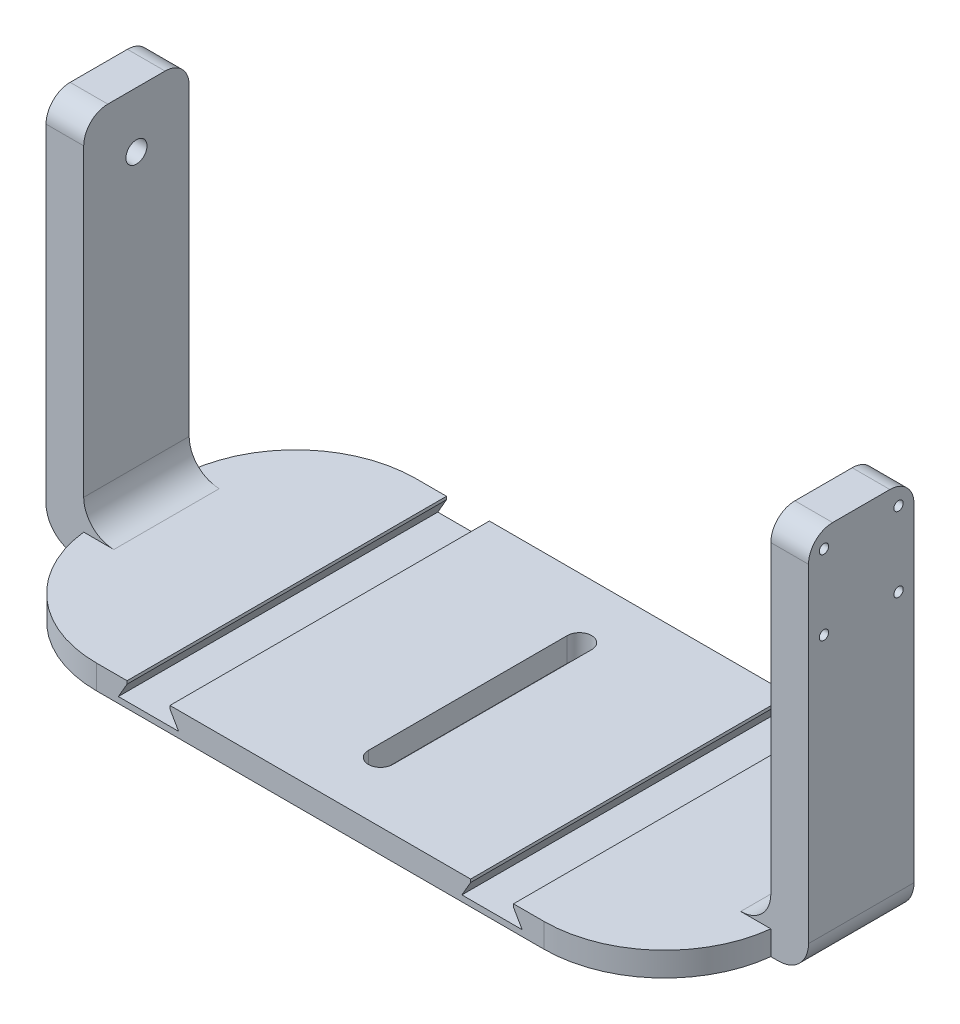
SolidWorks part; units mm, degrees
ref_plane "Front Plane" through (0, 0, 0) normal (0, 0, 1) x (1, 0, 0)
ref_plane "Top Plane" through (0, 0, 0) normal (0, 1, 0) x (1, 0, 0)
ref_plane "Right Plane" through (0, 0, 0) normal (1, 0, 0) x (0, 0, -1)
sketch "Sketch1" plane through (0, 0, 0) normal (0, 0, 1) x (1, 0, 0)
  line L0 (114, 8) -> (114, 0) construction
  line L1 (0, 0) -> (228, 0)
  line L2 (0, 0) -> (0, 8)
  line L3 (0, 8) -> (228, 8)
  line L4 (228, 0) -> (228, 8)
  line L5 (49.8868, 8) -> (49.8868, 7)
  line L7 (178.1132, 8) -> (163.8868, 8)
  line L8 (163.8868, 8) -> (163.8868, 7)
  line L9 (163.8868, 7) -> (161, 2)
  line L10 (161, 2) -> (181, 2)
  line L11 (178.1132, 8) -> (178.1132, 7)
  line L12 (178.1132, 7) -> (181, 2)
  line L13 (114, 4) -> (228, 4) construction
  line L14 (49.8868, 8) -> (64.1132, 8)
  line L15 (171, 2) -> (171, 8) construction
  line L16 (64.1132, 8) -> (64.1132, 7)
  line L17 (64.1132, 7) -> (67, 2)
  line L18 (67, 2) -> (47, 2)
  line L19 (49.8868, 7) -> (47, 2)
  line L25 (228, 0) -> (240.5, 0)
  line L26 (228, 0) -> (228, 127)
  line L27 (228, 127) -> (240.5, 127)
  line L28 (240.5, 0) -> (240.5, 127)
  line L29 (0, 0) -> (-12.5, 0)
  line L30 (0, 0) -> (0, 127)
  line L31 (0, 127) -> (-12.5, 127)
  line L32 (-12.5, 0) -> (-12.5, 127)
  point P7 (171, 4)
  dimension "D1" = 228
  dimension "D2" = 8
  dimension "D3" = 1
  dimension "D4" = 1
  dimension "D5" = 60
  dimension "D6" = 60
  dimension "D7" = 20
  dimension "D8" = 2
  dimension "D9" = 12.5
  dimension "D10" = 127
  dimension "D11" = 12.5
  dimension "D12" = 127
extrude "Boss-Extrude1" add sketch "Sketch1" against normal blind 106 contours L19 L5 L3 L2 L1 L4 L11 L12 L10 L9 L8 L16 L17 L18 | L26 L25 L28 L27 | L30 L29 L32 L31 region at (114, 3.9008, 0)
sketch "Sketch2" plane through (0, 127, 0) normal (0, 1, 0) x (1, 0, 0)
  line L0 (0, 106) -> (0, 0) construction
  line L1 (-12.5, 106) -> (0, 106)
  line L2 (-12.5, 106) -> (-12.5, 70.5)
  line L3 (-12.5, 70.5) -> (0, 70.5)
  line L4 (0, 106) -> (0, 70.5)
  line L5 (228, 106) -> (228, 0) construction
  line L6 (-12.5, 0) -> (0, 0)
  line L7 (-12.5, 0) -> (-12.5, 35.5)
  line L8 (-12.5, 35.5) -> (0, 35.5)
  line L9 (0, 0) -> (0, 35.5)
  line L10 (240.5, 106) -> (228, 106)
  line L11 (240.5, 106) -> (240.5, 70.5)
  line L12 (240.5, 70.5) -> (228, 70.5)
  line L13 (228, 106) -> (228, 70.5)
  line L14 (0, 106) -> (228, 106) construction
  line L15 (240.5, 0) -> (228, 0)
  line L16 (240.5, 0) -> (240.5, 35.5)
  line L17 (240.5, 35.5) -> (228, 35.5)
  line L18 (228, 0) -> (228, 35.5)
  line L19 (114, 106) -> (114, 0) construction
  line L20 (64.1132, 0) -> (163.8868, 0) construction
  line L21 (114, 20) -> (114, 86) construction
  line L22 (109.95, 20) -> (109.95, 86)
  line L23 (118.05, 20) -> (118.05, 86)
  line L24 (0, 53) -> (228, 53) construction
  line L27 (0, 106) -> (0, 0) construction
  line L28 (228, 106) -> (228, 0) construction
  arc A0 (109.95, 20) -> (118.05, 20) centre (114, 20) ccw
  arc A1 (118.05, 86) -> (109.95, 86) centre (114, 86) ccw
  point P30 (114, 53)
  point P35 (114, 90.05)
  point P36 (114, 15.95)
  point P41 (114, 106)
  point P44 (114, 53)
  dimension "D1" = 35
  dimension "D2" = 35.5
  dimension "D3" = 35.5
  dimension "D4" = 35
  dimension "D5" = 74.1
  dimension "D6" = 8.1
extrude "Cut-Extrude1" cut sketch "Sketch2" against normal blind 200
sketch "Sketch4" plane through (240.5, 0, 0) normal (1, 0, 0) x (0, 0, -1)
  line L0 (70.5, 0) -> (35.5, 0) construction
  line L1 (70.5, 127) -> (35.5, 127) construction
  line L2 (53, 127) -> (53, 0) construction
  line L3 (53, 127) -> (53, 101.5) construction
  line L4 (53, 108.5) -> (35.5, 108.5) construction
  line L5 (35.5, 0) -> (35.5, 127) construction
  circle A3 centre (40.625, 120.875) radius 1.55
  circle A4 centre (40.625, 96.125) radius 1.55
  circle A5 centre (65.375, 96.125) radius 1.55
  circle A6 centre (65.375, 120.875) radius 1.55
  point P1 (53, 126.7598)
  dimension "D2" = 18.5
  dimension "D3" = 101.5
  dimension "D7" = 3.1
  dimension "D8" = 3.1
  dimension "D5" = 12.375
  dimension "D10" = 12.375
fillet "Fillet3" radius 8 4 edges at (234.25, 127, -70.5) (234.25, 127, -35.5) (-6.25, 127, -70.5) (-6.25, 127, -35.5)
fillet "Fillet4" radius 10 4 edges at (228, 8, -53) (240.5, 0, -53) (-12.5, 0, -53) (0, 8, -53)
fillet "Fillet5" radius 40 4 edges at (228, 4, -106) (0, 4, -106) (0, 4, 0) (228, 4, 0)
sketch "Sketch5" plane through (0, 0, 0) normal (1, 0, 0) x (0, 0, -1)
  line L0 (62.5, 127) -> (43.5, 127) construction
  line L1 (35.5, 18) -> (35.5, 119) construction
  circle A0 centre (53, 108.5) radius 9.5
  circle A1 centre (53, 108.5) radius 3.5
  dimension "D1" = 19
  dimension "D2" = 7
  dimension "D3" = 18.5
  dimension "D4" = 17.5
extrude "Cut-Extrude5" cut sketch "Sketch5" against normal blind 25 contours A1
extrude "Cut-Extrude6" cut sketch "Sketch5<3>" against normal blind 7 from offset 6 offset against normal yes
sketch "Sketch5<3>" plane through (0, 0, 0) normal (1, 0, 0) x (0, 0, -1) same geometry as "Sketch5"
extrude "Cut-Extrude7" cut sketch "Sketch4" against normal blind 16
